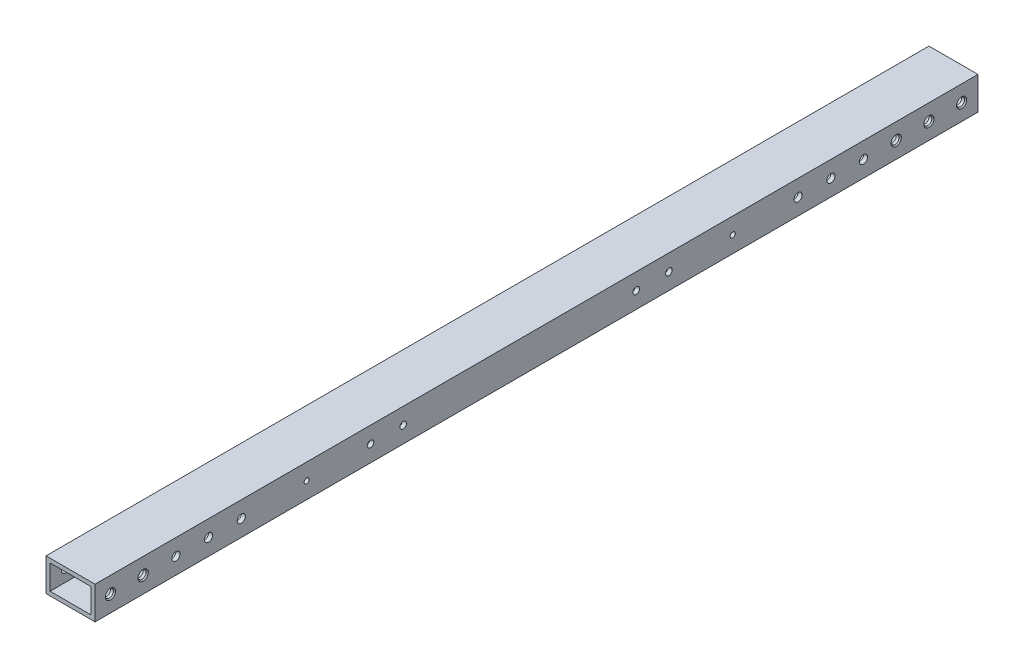
SolidWorks part; units mm, degrees
ref_plane "Front Plane" through (0, 0, 0) normal (0, 0, 1) x (1, 0, 0)
ref_plane "Top Plane" through (0, 0, 0) normal (0, 1, 0) x (1, 0, 0)
ref_plane "Right Plane" through (0, 0, 0) normal (1, 0, 0) x (0, 0, -1)
sketch "Sketch1" plane through (0, 0, 0) normal (0, 0, 1) x (1, 0, 0)
  line L0 (-15.875, 9.525) -> (15.875, 9.525)
  line L2 (-19.05, 12.7) -> (19.05, 12.7)
  line L3 (-19.05, 12.7) -> (-19.05, -12.7)
  line L4 (-19.05, -12.7) -> (19.05, -12.7)
  line L5 (19.05, 12.7) -> (19.05, -12.7)
  line L10 (15.875, 9.525) -> (15.875, -9.525)
  line L11 (-15.875, -9.525) -> (15.875, -9.525)
  line L12 (-15.875, 9.525) -> (-15.875, -9.525)
  point P12 (0, 12.7)
  point P14 (19.05, 0)
  dimension "Wall Thickness" = 3.175
  dimension "Outside Width" = 38.1
  dimension "Outside Height" = 25.4
  dimension "Inside Height" = 19.05
  dimension "Inside Width" = 31.75
sketch "Sketch2" plane through (0, 0, 0) normal (1, 0, 0) x (0, 0, -1)
  line L0 (342.9, 0) -> (-342.9, 0)
  point P4 (0, 0)
  point P7 (-342.9, 0)
  point P10 (342.9, 0)
  dimension "Length" = 685.8
sketch "Sketch3" plane through (0, 0, 0) normal (0, 0, 1) x (1, 0, 0)
  line L21 (19.05, 12.7) -> (-19.05, 12.7)
  line L22 (19.05, -12.7) -> (19.05, 12.7)
  line L23 (-19.05, -12.7) -> (19.05, -12.7)
  line L24 (-19.05, 12.7) -> (-19.05, -12.7)
  line L25 (19.05, 12.7) -> (-19.05, 12.7)
  line L26 (19.05, -12.7) -> (19.05, 12.7)
  line L27 (-19.05, -12.7) -> (19.05, -12.7)
  line L28 (-19.05, 12.7) -> (-19.05, -12.7)
  line L29 (15.875, 9.525) -> (-15.875, 9.525)
  line L30 (15.875, -9.525) -> (15.875, 9.525)
  line L31 (-15.875, -9.525) -> (15.875, -9.525)
  line L32 (-15.875, 9.525) -> (-15.875, -9.525)
  line L33 (15.875, 9.525) -> (-15.875, 9.525)
  line L34 (15.875, -9.525) -> (15.875, 9.525)
  line L35 (-15.875, -9.525) -> (15.875, -9.525)
  line L36 (-15.875, 9.525) -> (-15.875, -9.525)
  dimension "D1" = 0
  dimension "D2" = 0
extrude "Boss-Extrude1" add sketch "Sketch3" along normal up to vertex (342.9 mm away) and the other way up to vertex (342.9 mm away) up to point (0, 0, 342.9) other way up to point (0, 0, -342.9)
sketch "Drawing Reference" plane through (0, 0, 0) normal (1, 0, 0) x (0, 0, -1)
  line L0 (-342.9, 0) -> (342.9, 0) construction
  line L1 (0, -12.7) -> (0, 12.7) construction
  line L2 (-342.9, -12.7) -> (342.9, -12.7) construction
  line L5 (-342.9, 12.7) -> (342.9, 12.7) construction
  point P7 (-315.468, 0)
  point P8 (315.468, 0)
  dimension "D1" = 27.432
sketch "Sketch4" plane through (-19.05, 0, 0) normal (-1, 0, 0) x (0, 0, 1)
  line L0 (-342.9, 0) -> (-330.2, 0)
  line L1 (-342.9, 12.7) -> (-342.9, -12.7) construction
  line L2 (-330.2, 0) -> (-304.8, 0)
  line L3 (-304.8, 0) -> (-279.4, 0)
  line L4 (-279.4, 0) -> (-254, 0)
  line L5 (-254, 0) -> (-228.6, 0)
  line L6 (-228.6, 0) -> (-203.2, 0)
  line L7 (342.9, 0) -> (330.9118, 0)
  line L8 (342.9, 12.7) -> (342.9, -12.7) construction
  line L9 (330.9118, 0) -> (305.5118, 0)
  line L10 (305.5118, 0) -> (280.1118, 0)
  line L11 (280.1118, 0) -> (254.7118, 0)
  line L12 (254.7118, 0) -> (229.3118, 0)
hole_wizard "1/4 (0.25) Diameter Hole2" positions "Sketch7" profile "Sketch8" hole size "1/4" standard "ANSI Inch" end condition through all
sketch "Sketch7" plane through (-19.05, 0, 0) normal (-1, 0, 0) x (0, 0, 1)
  point P0 (-330.2, 0)
  point P3 (-304.8, 0)
  point P7 (330.9118, 0)
  point P11 (-279.4, 0)
  point P14 (305.5118, 0)
sketch "Sketch8" plane through (-19.05, 0, -330.2) normal (0, 1, 0) x (0, 0, 1)
  line L0 (0, 0) -> (0, 38.1)
  line L1 (0, 38.1) -> (3.9624, 38.1)
  line L2 (3.175, 37.1942) -> (3.175, 0)
  line L5 (3.175, 0) -> (0, 0)
  line L7 (3.9624, 38.1) -> (3.175, 37.1942)
  line L8 (-3.9624, 38.1) -> (-3.175, 37.1942) construction
  line L11 (0, -6.35) -> (0, 107.95) construction
  dimension "Thru Hole Dia." = 6.35
  dimension "Thru Hole Depth" = 38.1
  dimension "Far C'Sink Dia." = 7.9248
  dimension "Far C'Sink Angle" = 82
hole_wizard "1/4 (0.25) Diameter Hole3" positions "Sketch9" profile "Sketch10" hole size "1/4" standard "ANSI Inch" end condition through all
sketch "Sketch9" plane through (19.05, 0, 0) normal (1, 0, 0) x (0, 0, -1)
  point P0 (-280.1118, 0)
  point P3 (-254.7118, 0)
  point P6 (-229.3118, 0)
  point P9 (254, 0)
  point P12 (228.6, 0)
  point P15 (203.2, 0)
sketch "Sketch10" plane through (19.05, 0, 280.1118) normal (0, 1, 0) x (0, 0, -1)
  line L0 (0, 0) -> (0, 38.1)
  line L1 (0, 38.1) -> (3.175, 38.1)
  line L2 (3.175, 38.1) -> (3.175, 0)
  line L5 (3.175, 0) -> (0, 0)
  line L11 (0, -6.35) -> (0, 107.95) construction
  dimension "Thru Hole Dia." = 6.35
  dimension "Thru Hole Depth" = 38.1
hole_wizard "5/32 (0.15625) Diameter Hole1" positions "Sketch11" profile "Sketch12" hole size "5/32" standard "ANSI Inch" end condition through all
sketch "Sketch11" plane through (19.05, 0, 0) normal (1, 0, 0) x (0, 0, -1)
  point P0 (152.4, 0)
  point P3 (-178.5118, 0)
sketch "Sketch12" plane through (19.05, 0, -152.4) normal (0, 1, 0) x (0, 0, -1)
  line L0 (0, 0) -> (0, 38.1)
  line L1 (0, 38.1) -> (1.9844, 38.1)
  line L2 (1.9844, 38.1) -> (1.9844, 0)
  line L5 (1.9844, 0) -> (0, 0)
  line L11 (0, -6.35) -> (0, 107.95) construction
  dimension "Thru Hole Dia." = 3.9688
  dimension "Thru Hole Depth" = 38.1
sketch "Sketch13" plane through (19.05, 0, 0) normal (1, 0, 0) x (0, 0, -1)
  line L0 (-103.5434, 0) -> (-128.9434, 0)
  line L1 (77.4316, 0) -> (102.8316, 0)
hole_wizard "#10 Clearance Hole1" positions "Sketch14" profile "Sketch15" hole size "#10" standard "ANSI Inch" end condition through all
sketch "Sketch14" plane through (19.05, 0, 0) normal (1, 0, 0) x (0, 0, -1)
  point P0 (-128.9434, 0)
  point P3 (-103.5434, 0)
  point P7 (77.4316, 0)
  point P10 (102.8316, 0)
sketch "Sketch15" plane through (19.05, 0, 128.9434) normal (0, 1, 0) x (0, 0, -1)
  line L0 (0, 0) -> (0, 38.1)
  line L1 (0, 38.1) -> (2.5527, 38.1)
  line L2 (2.5527, 38.1) -> (2.5527, 0)
  line L5 (2.5527, 0) -> (0, 0)
  line L11 (0, -6.35) -> (0, 107.95) construction
  dimension "Thru Hole Dia." = 5.1054
  dimension "Thru Hole Depth" = 38.1
equation "\"D1@Drawing Reference\"=\"Outside Width@Sketch1\" * 0.72"
